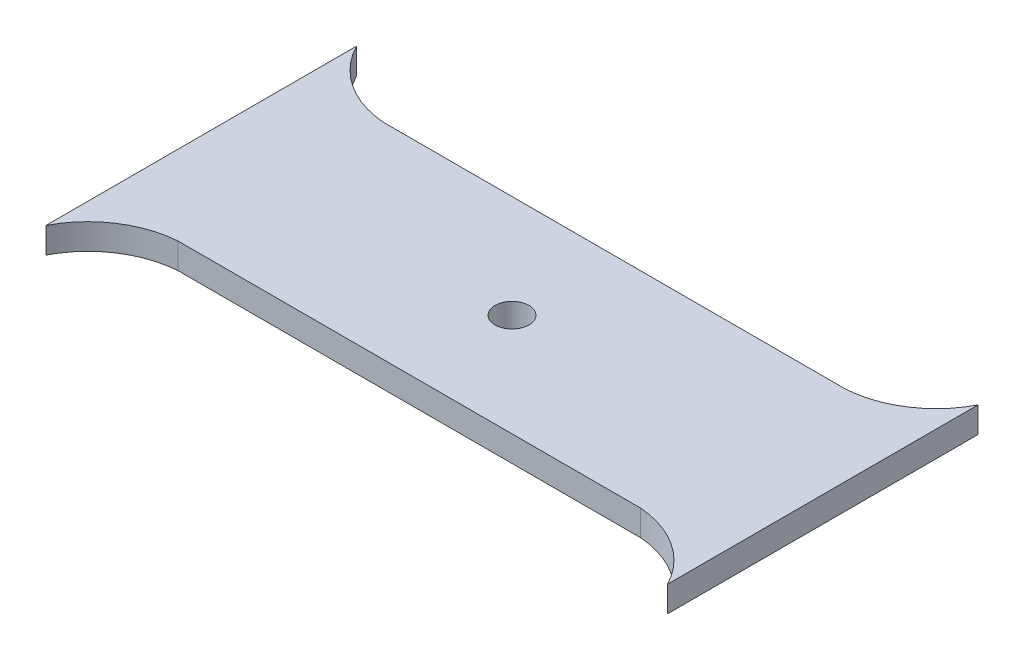
SolidWorks part; units mm, degrees
material "AISI 4340 Steel, normalized"
ref_plane "Front Plane" through (0, 0, 0) normal (0, 0, 1) x (1, 0, 0)
ref_plane "Top Plane" through (0, 0, 0) normal (0, 1, 0) x (1, 0, 0)
ref_plane "Right Plane" through (0, 0, 0) normal (1, 0, 0) x (0, 0, -1)
sketch "Sketch1" plane through (0, 0, 0) normal (0, 1, 0) x (1, 0, 0)
  line L0 (57.15, 25.4) -> (-57.15, 25.4)
  line L1 (-76.8079, 38.3776) -> (-76.8079, -38.3776)
  line L2 (0, 25.4) -> (0, 47.1974)
  line L3 (25.4, 0) -> (46.398, 0)
  line L4 (57.15, -25.4) -> (-57.15, -25.4)
  line L5 (76.8079, 38.3776) -> (76.8079, -38.3776)
  circle A0 centre (0, 0) radius 25.4
  circle A1 centre (0, 0) radius 4.191
  arc A2 (-57.15, 25.4) -> (-76.8079, 38.3776) centre (-55.3758, 49.4647) cw
  arc A3 (-57.15, -25.4) -> (-76.8079, -38.3776) centre (-55.3758, -49.4647) ccw
  arc A4 (57.15, -25.4) -> (76.8079, -38.3776) centre (55.3758, -49.4647) cw
  arc A5 (57.15, 25.4) -> (76.8079, 38.3776) centre (55.3758, 49.4647) ccw
  point P16 (0, -25.4)
  dimension "D1" = 50.8
  dimension "D4" = 8.382
  dimension "D3" = 24.13
  dimension "D2" = 57.15
extrude "Boss-Extrude1" add sketch "Sketch1" along normal blind 6.35 contours A0 A1 | A0 | A0 | A0 | A0 region at (49.3244, 0, 0) region at (-49.3244, 0, 0) region at (17.4525, 0, -17.4525)
sketch "Sketch2" plane through (0, 0, 0) normal (0, -1, 0) x (1, 0, 0)
  circle A0 centre (0, 0) radius 10.16
  circle A1 centre (0, 0) radius 4.191 construction
  circle A2 centre (0, 0) radius 4.191
  dimension "D1" = 20.32
extrude "Boss-Extrude2" add sketch "Sketch2" along normal blind 11.43
sketch "Sketch3" plane through (0, -11.43, 0) normal (0, -1, 0) x (1, 0, 0)
  circle A0 centre (0, 0) radius 11.43
  circle A1 centre (0, 0) radius 10.16 construction
  circle A2 centre (0, 0) radius 10.16
  dimension "D1" = 22.86
extrude "Boss-Extrude3" add sketch "Sketch3" against normal blind 3.175
